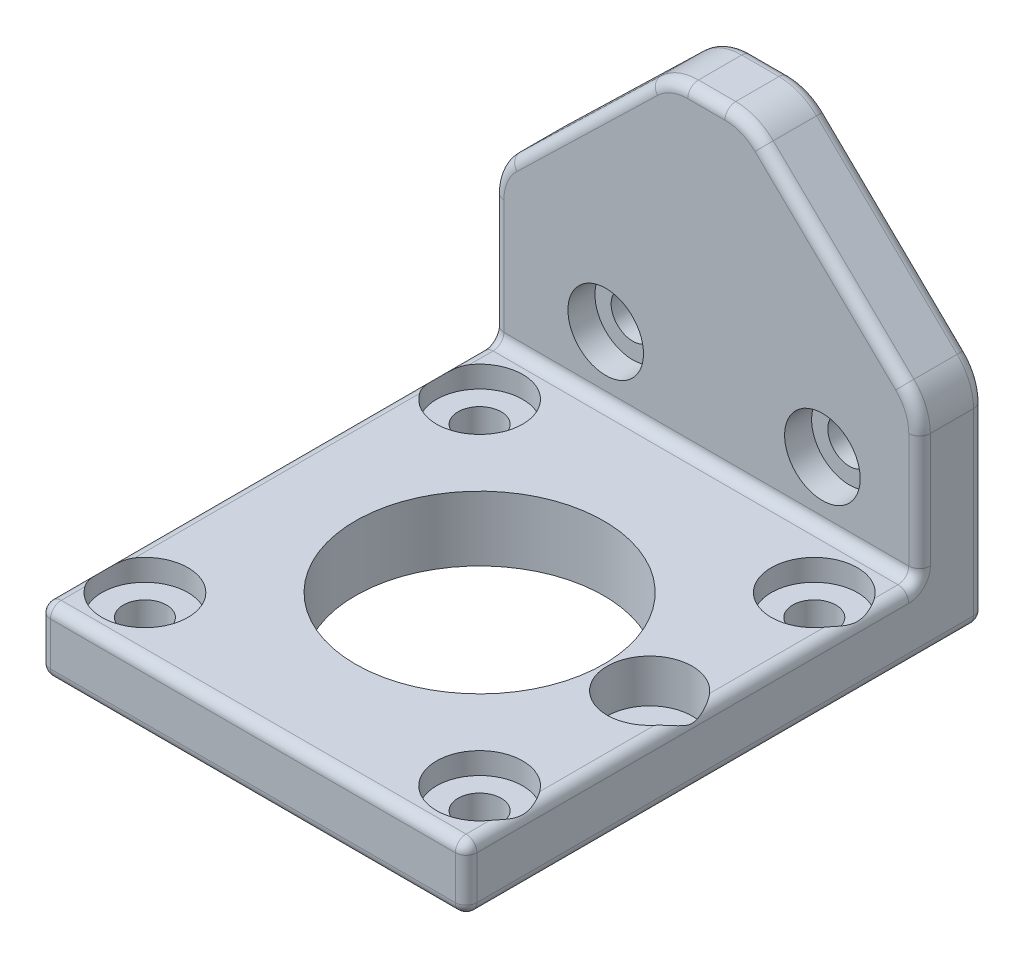
SolidWorks part; units mm, degrees
ref_plane "Front Plane" through (0, 0, 0) normal (0, 0, 1) x (1, 0, 0)
ref_plane "Top Plane" through (0, 0, 0) normal (0, 1, 0) x (1, 0, 0)
ref_plane "Right Plane" through (0, 0, 0) normal (1, 0, 0) x (0, 0, -1)
sketch "Sketch1" plane through (0, 0, 0) normal (0, 1, 0) x (1, 0, 0)
  line L1 (-19.75, 21) -> (19.75, 21)
  line L2 (-19.75, 21) -> (-19.75, -21)
  line L3 (-19.75, -21) -> (19.75, -21)
  line L4 (19.75, 21) -> (19.75, -21)
  line L5 (-19.75, 21) -> (19.75, -21) construction
  line L6 (-19.75, -21) -> (19.75, 21) construction
  point P0 (0, 0)
  dimension "D1" = 39.5
  dimension "D2" = 42
extrude "Boss-Extrude1" add sketch "Sketch1" along normal blind 6
sketch "Sketch3" plane through (0, 6, 0) normal (0, 1, 0) x (1, 0, 0)
  line L0 (0, -15.5) -> (0, 15.5) construction
  line L1 (-15.5, 0) -> (15.5, 0) construction
  line L2 (-15.5, 15.5) -> (15.5, 15.5) construction
  line L3 (15.5, 15.5) -> (15.5, -15.5) construction
  line L4 (15.5, -15.5) -> (-15.5, -15.5) construction
  line L5 (-15.5, -15.5) -> (-15.5, 15.5) construction
  circle A0 centre (-15.5, 15.5) radius 3.9905
  circle A1 centre (15.5, 15.5) radius 3.9905
  circle A2 centre (-15.5, -15.5) radius 3.9905
  circle A3 centre (15.5, -15.5) radius 3.9905
  point P12 (0, 0)
  point P16 (0, 0)
  point P17 (0, 15.5)
  point P20 (15.5, 0)
  dimension "D1" = 7.981
  dimension "D2" = 31
  dimension "D3" = 31
extrude "Cut-Extrude1" cut sketch "Sketch3" against normal blind 2
sketch "Sketch4" plane through (0, 6, 0) normal (0, 1, 0) x (1, 0, 0)
  circle A0 centre (0, 0) radius 11.5
  circle A1 centre (15.5, 15.5) radius 2
  circle A2 centre (-15.5, 15.5) radius 2
  circle A3 centre (-15.5, -15.5) radius 2
  circle A4 centre (15.5, -15.5) radius 2
  dimension "D1" = 4
  dimension "D2" = 23
extrude "Cut-Extrude2" cut sketch "Sketch4" against normal through all
sketch "Sketch5" plane through (0, 0, -21) normal (0, 0, -1) x (-1, 0, 0)
  line L0 (0, 9.875) -> (0, 19.75) construction
  line L2 (-19.75, 19.75) -> (-19.75, 0)
  line L3 (-19.75, 0) -> (19.75, 0)
  line L4 (19.75, 19.75) -> (19.75, 0)
  line L5 (-19.75, 19.75) -> (19.75, 0) construction
  line L6 (-19.75, 0) -> (19.75, 19.75) construction
  line L7 (-3.75, 35.25) -> (3.75, 35.25)
  line L13 (3.75, 35.25) -> (19.75, 19.75)
  line L14 (-3.75, 35.25) -> (-19.75, 19.75)
  point P0 (0, 9.875)
  point P6 (0, 27.5)
  dimension "D1" = 35.25
  dimension "D2" = 19.75
  dimension "D3" = 16
  dimension "D4" = 16
  dimension "D5" = 15.5
extrude "Boss-Extrude2" add sketch "Sketch5" along normal blind 6
sketch "Sketch6" plane through (0, 0, -21) normal (0, 0, 1) x (1, 0, 0)
  line L0 (-9.32, 11.75) -> (10.75, 11.75) construction
  line L1 (-19.75, 6.845) -> (0.715, 6.845) construction
  line L2 (-19.75, 6) -> (-19.75, 19.75) construction
  line L3 (0.715, 6.845) -> (0.715, 11.75) construction
  circle A0 centre (-9.32, 11.75) radius 3.5
  circle A1 centre (10.75, 11.75) radius 3.5
  dimension "D1" = 7
  dimension "D2" = 7
  dimension "D3" = 20.465
  dimension "D4" = 20.07
  dimension "D5" = 11.75
extrude "Cut-Extrude3" cut sketch "Sketch6" against normal blind 2.5
sketch "Sketch7" plane through (0, 0, -21) normal (0, 0, 1) x (1, 0, 0)
  circle A0 centre (-9.32, 11.75) radius 2
  circle A1 centre (10.75, 11.75) radius 2
  dimension "D1" = 4
extrude "Cut-Extrude4" cut sketch "Sketch7" against normal through all
fillet "Fillet1" radius 5 4 edges at (19.75, 19.75, -24) (3.75, 35.25, -24) (-3.75, 35.25, -24) (-19.75, 19.75, -24)
sketch "Sketch8" plane through (0, 6, 0) normal (0, 1, 0) x (1, 0, 0)
  line L0 (0, 0) -> (15.75, 0) construction
  circle A0 centre (15.75, 0) radius 3.9365
  dimension "D1" = 7.873
  dimension "D2" = 15.75
extrude "Cut-Extrude5" cut sketch "Sketch8" against normal blind 4
fillet "Fillet2" radius 1 28 edges at (19.75, 6, 0) (19.75, 11.8161, -21) (19.3541, 19.5823, -21) (11.7166, 27.5323, -21) (3.602, 34.8844, -21) (0, 35.25, -21) (-3.602, 34.8844, -21) (-11.7166, 27.5323, -21) (-19.3541, 19.5823, -21) (-19.75, 11.8161, -21) (-19.75, 8.8161, -27) (-19.3541, 19.5823, -27) (-11.7166, 27.5323, -27) (-3.602, 34.8844, -27) (0, 35.25, -27) (3.602, 34.8844, -27) (11.7166, 27.5323, -27) (19.3541, 19.5823, -27) (19.75, 8.8161, -27) (0, 0, -27) (19.75, 0, -3) (0, 0, 21) (-19.75, 0, -3) (0, 6, 21) (-19.75, 6, 0) (0, 6, -21) (19.75, 3, 21) (-19.75, 3, 21)
